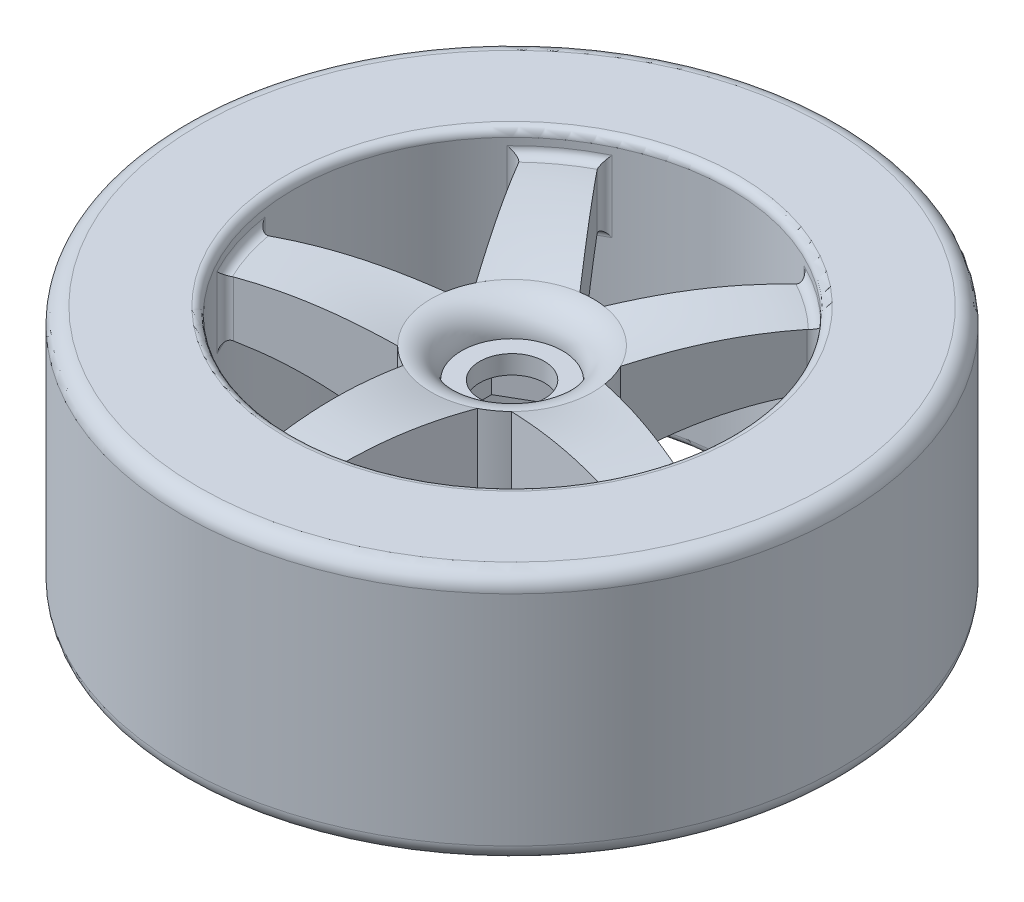
SolidWorks part; units mm, degrees
ref_plane "Front Plane" through (0, 0, 0) normal (0, 0, 1) x (1, 0, 0)
ref_plane "Top Plane" through (0, 0, 0) normal (0, 1, 0) x (1, 0, 0)
ref_plane "Right Plane" through (0, 0, 0) normal (1, 0, 0) x (0, 0, -1)
sketch "Sketch1" plane through (0, 0, 0) normal (0, 1, 0) x (1, 0, 0)
  circle A0 centre (0, 0) radius 40.75
  circle A1 centre (0, 0) radius 27
  dimension "D1" = 81.5
  dimension "D2" = 54
extrude "Boss-Extrude1" add sketch "Sketch1" along normal blind 31
ref_plane "Plane1" through (0, 16.8, 0) normal (0, 1, 0) x (1, 0, 0)
sketch "Sketch2" plane through (0, 16.8, 0) normal (0, 1, 0) x (1, 0, 0)
  circle A0 centre (0, 0) radius 10
  dimension "D1" = 20
extrude "Boss-Extrude2" add sketch "Sketch2" along normal blind 10 separate body
sketch "Sketch5" plane through (0, 0, 0) normal (0, 0, 1) x (1, 0, 0)
  line L0 (-27, 31) -> (-27, 28)
  line L1 (-27, 31) -> (-27, 0) construction
  line L2 (27, 31) -> (-27, 31) construction
  line L3 (-27, 28) -> (-27, 21.3)
  line L4 (-10, 16.8) -> (-10, 26.8)
  line L5 (0, 0) -> (0, 26.8) construction
  spline S0 degree 2 poles (-10, 26.8) (-18.4005, 28.9373) (-27, 28) knots 0 0 0 1 1 1
  spline S1 degree 2 poles (-27, 21.3) (-17.7207, 21.1825) (-10, 16.8) knots 0 0 0 1 1 1
  dimension "D6" = 6.7
  dimension "D4" = 17.7775
  dimension "D1" = 3
  dimension "D2" = 8.9966
  dimension "D3" = 2.796
  dimension "D5" = 2.5732
revolve "Revolve1" add sketch "Sketch5" angle 360 about L5 region at (-17.9355, 23.7749, 0)
sketch "Sketch6" plane through (0, 26.8, 0) normal (0, 1, 0) x (1, 0, 0)
  line L0 (0, 0) -> (0, 27) construction
  line L1 (-13, 23.6643) -> (-1.5, 9.8869)
  line L2 (13, 23.6643) -> (1.5, 9.8869)
  circle A0 centre (0, 0) radius 27 construction
  circle A3 centre (0, 0) radius 10 construction
  arc A4 (13, 23.6643) -> (-13, 23.6643) centre (0, 0) ccw
  arc A7 (1.5, 9.8869) -> (-1.5, 9.8869) centre (0, 0) ccw
  dimension "D1" = 26
  dimension "D2" = 3
extrude "Cut-Extrude1" cut sketch "Sketch6" against normal through all both and the other way through all contours L1 A7 L2 A4
pattern_circular "CirPattern2" count 5 over 360 about axis through (0, 0, 0) along (0, 1, 0) of "Cut-Extrude1" reverse direction yes
sketch "Sketch8" plane through (0, 16.8, 0) normal (0, -1, 0) x (1, 0, 0)
  line L1 (0, 6.9282) -> (-6, 3.4641)
  line L2 (-6, 3.4641) -> (-6, -3.4641)
  line L3 (-6, -3.4641) -> (0, -6.9282)
  line L4 (0, -6.9282) -> (6, -3.4641)
  line L5 (6, -3.4641) -> (6, 3.4641)
  line L6 (6, 3.4641) -> (0, 6.9282)
  circle A0 centre (0, 0) radius 6 construction
  dimension "D1" = 12
extrude "Cut-Extrude2" cut sketch "Sketch8" against normal blind 4
fillet "Fillet1" radius 1 22 edges at (15.8702, 28, -21.8435) (13, 24.65, -23.6643) (15.8702, 21.3, -21.8435) (18.4889, 24.65, -19.6764) (0, 31, 27) (0, 0, 27) (-13, 24.65, -23.6643) (-15.8702, 28, -21.8435) (-18.4889, 24.65, -19.6764) (-15.8702, 21.3, -21.8435) (-25.6785, 28, 8.3435) (-24.4268, 24.65, 11.5036) (-25.6785, 21.3, 8.3435) (-26.5233, 24.65, 5.0511) (0, 28, 27) (3.3923, 24.65, 26.786) (0, 21.3, 27) (-3.3923, 24.65, 26.786) (25.6785, 28, 8.3435) (26.5233, 24.65, 5.0511) (25.6785, 21.3, 8.3435) (24.4268, 24.65, 11.5036)
fillet "Fillet2" radius 2 2 edges at (0, 0, 40.75) (0, 31, 40.75)
sketch "Sketch9" plane through (0, 26.8, 0) normal (0, 1, 0) x (1, 0, 0)
  circle A0 centre (0, 0) radius 6.25
  circle A1 centre (0, 0) radius 2
  dimension "D1" = 12.5
  dimension "D2" = 4
extrude "Cut-Extrude3" cut sketch "Sketch9" against normal blind 3.7
sketch "Sketch10" plane through (0, 23.1, 0) normal (0, 1, 0) x (1, 0, 0)
  circle A0 centre (0, 0) radius 4
  dimension "D1" = 8
extrude "Cut-Extrude4" cut sketch "Sketch10" against normal through all both and the other way through all
fillet "Fillet4" radius 3.75 1 edges at (0, 26.8, 6.25)
